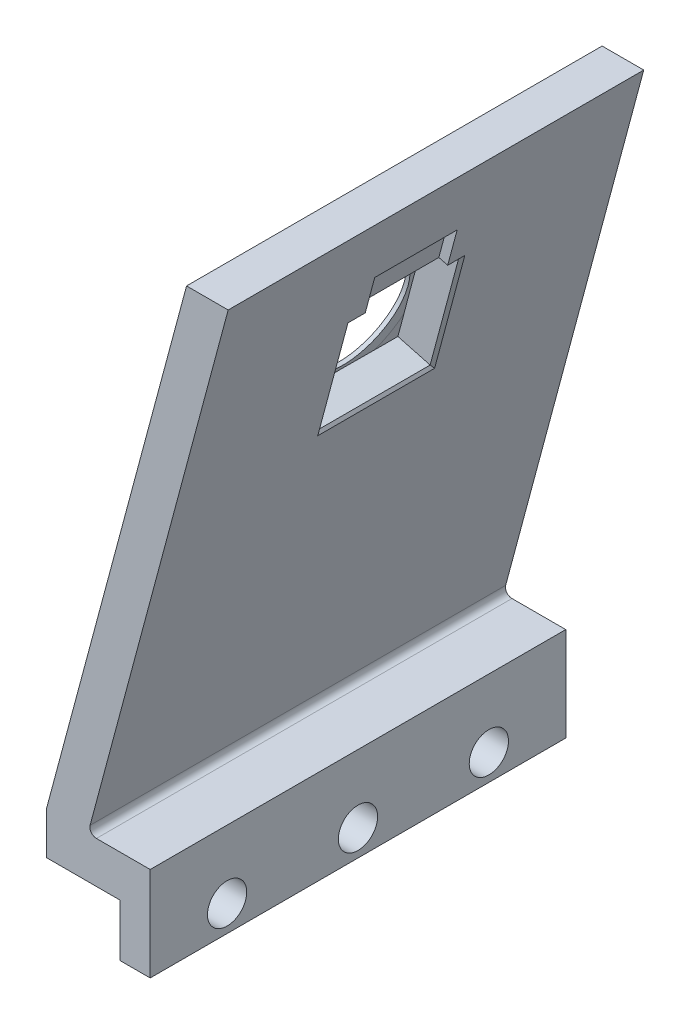
SolidWorks part; units mm, degrees
ref_plane "Plan de face" through (0, 0, 0) normal (0, 0, 1) x (1, 0, 0)
ref_plane "Plan de dessus" through (0, 0, 0) normal (0, 1, 0) x (1, 0, 0)
ref_plane "Plan de droite" through (0, 0, 0) normal (1, 0, 0) x (0, 0, -1)
sketch "Esquisse1" plane through (0, 0, 0) normal (0, 0, 1) x (1, 0, 0)
  line L0 (0, 0) -> (10.718, 40)
  line L1 (10.718, 40) -> (13.898, 40)
  line L2 (13.898, 40) -> (3.18, 0)
  line L3 (3.18, 0) -> (0, 0)
  line L5 (0, 0) -> (7.94, 0)
  line L6 (0, 0) -> (0, -3.18)
  line L7 (0, -3.18) -> (7.94, -3.18)
  line L8 (7.94, 0) -> (7.94, -3.18)
  line L9 (5.6434, -3.18) -> (7.94, -3.18)
  line L10 (5.6434, -3.18) -> (5.6434, -7.18)
  line L11 (5.6434, -7.18) -> (7.94, -7.18)
  line L12 (7.94, -3.18) -> (7.94, -7.18)
  dimension "D1" = 75
  dimension "D2" = 3.18
  dimension "D3" = 40
  dimension "D4" = 7.94
  dimension "D5" = 4
  dimension "D6" = 3.18
extrude "Boss.-Extru.1" add sketch "Esquisse1" along normal blind 31.75 contours L3 L2 L1 L0 | L8 L5 L3 L6 L7 | L12 L11 L10 L9 region at (6.949, 20, 0) region at (3.97, -1.59, 0)
sketch "Esquisse2" plane through (2.967, -0.795, 0) normal (0.9659, -0.2588, 0) x (0, 0, -1)
  line L0 (0, 42.2341) -> (0, 0.823) construction
  line L1 (-20.41, 34.353) -> (-11.88, 34.353)
  line L2 (-20.41, 34.353) -> (-20.41, 25.823)
  line L3 (-20.41, 25.823) -> (-11.88, 25.823)
  line L4 (-11.88, 34.353) -> (-11.88, 25.823)
  line L5 (-31.75, 0.823) -> (0, 0.823) construction
  dimension "D1" = 8.53
  dimension "D2" = 8.53
  dimension "D3" = 11.88
  dimension "D4" = 25
extrude "Enlèv. mat.-Extru.1" cut sketch "Esquisse2" against normal blind 2.75
sketch "Esquisse3" plane through (0.3107, -0.0832, 0) normal (0.9659, -0.2588, 0) x (0, 0, -1)
  line L0 (-31.75, 2.055) -> (0, 2.055) construction
  circle A0 centre (-16.145, 30.055) radius 3.98
  point P2 (0, 0)
  point P3 (-16.145, 34.035)
  dimension "D1" = 7.96
  dimension "D2" = 28
extrude "Enlèv. mat.-Extru.2" cut sketch "Esquisse3" against normal blind 31.75
chamfer "Chanfrein3" distance 0.92 angle 1 1 edges at (9.1196, 32.7921, 16.145) first distance on face at (9.1196, 32.7921, 16.145)
sketch "Esquisse5" plane through (2.967, -0.795, 0) normal (0.9659, -0.2588, 0) x (0, 0, -1)
  line L0 (-11.88, 34.353) -> (-20.41, 34.353) construction
  line L6 (-19.29, 37.353) -> (-12.99, 37.353)
  line L7 (-19.29, 37.353) -> (-19.29, 34.353)
  line L8 (-19.29, 34.353) -> (-12.99, 34.353)
  line L9 (-12.99, 37.353) -> (-12.99, 34.353)
  line L10 (-20.41, 34.353) -> (-20.41, 32.4674) construction
  dimension "D1" = 1.12
  dimension "D2" = 3
  dimension "D3" = 6.3
extrude "Enlèv. mat.-Extru.3" cut sketch "Esquisse5" against normal blind 0.7
fillet "Chanfrein4" radius 0.2 8 edges at (10.7543, 28.2678, 20.41) (9.6505, 24.1481, 16.145) (10.7543, 28.2678, 11.88) (11.8582, 32.3875, 12.435) (11.5201, 32.4781, 12.99) (11.1821, 32.5687, 16.14) (11.5201, 32.4781, 19.29) (11.8582, 32.3875, 19.85) profile chamfer
sketch "Esquisse6" plane through (7.94, 0, 0) normal (1, 0, 0) x (0, 0, -1)
  line L1 (-31.75, 0) -> (-31.75, -7.18) construction
  line L2 (-31.75, -7.18) -> (0, -7.18) construction
  circle A0 centre (-25.875, -5.18) radius 1.5
  circle A1 centre (-15.875, -5.18) radius 1.5
  circle A2 centre (-5.875, -5.18) radius 1.5
  dimension "D1" = 3
  dimension "D4" = 2
  dimension "D5" = 3
  dimension "D2" = 10
  dimension "D3" = 15.875
extrude "Enlèv. mat.-Extru.4" cut sketch "Esquisse6" against normal blind 14.7
fillet "Congé3" radius 0.5 1 edges at (3.18, 0, 15.875)
